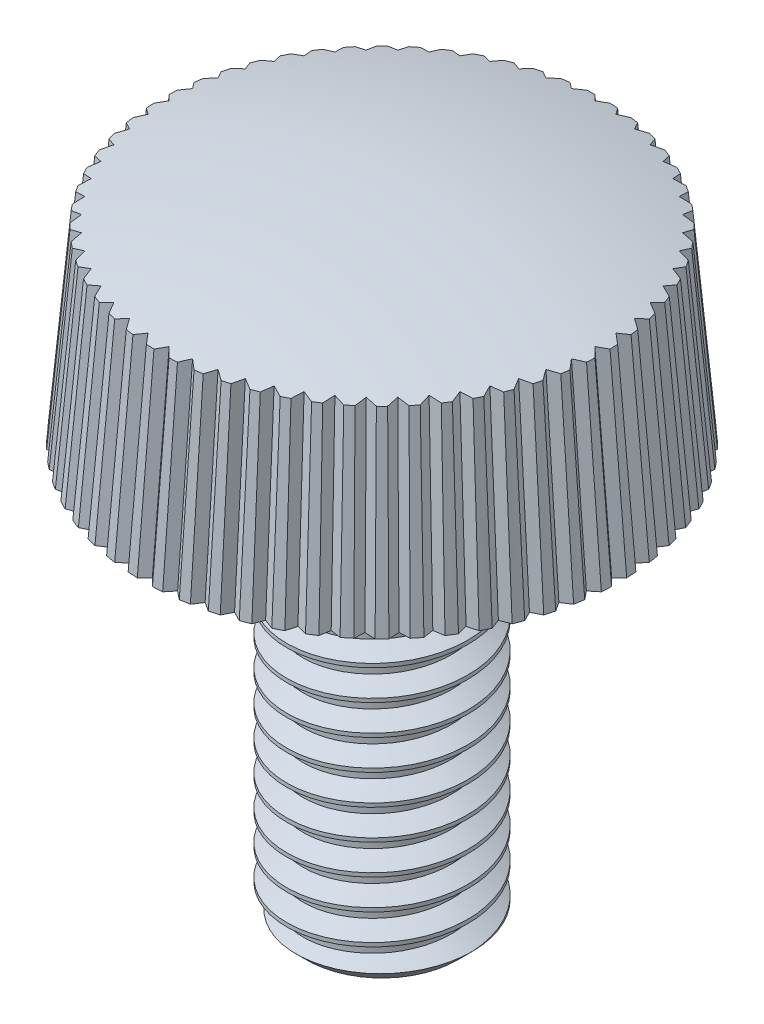
SolidWorks part; units mm, degrees
ref_plane "Front Plane" through (0, 0, 0) normal (0, 0, 1) x (1, 0, 0)
ref_plane "Top Plane" through (0, 0, 0) normal (0, 1, 0) x (1, 0, 0)
ref_plane "Right Plane" through (0, 0, 0) normal (1, 0, 0) x (0, 0, -1)
sketch "Sketch2" plane through (0, 0, 0) normal (0, 0, 1) x (1, 0, 0)
  line L0 (0, 0) -> (0, -2)
  line L1 (0, -2) -> (3.5, -2)
  line L2 (3.5, -2) -> (3.5, -8.78)
  line L3 (3.5, -8.78) -> (5, -8.78)
  line L4 (5, -8.78) -> (5, -7.28)
  line L5 (5, -7.28) -> (7.85, -7.28)
  line L6 (7.85, -7.28) -> (7.3006, -1)
  arc A0 (0, 0) -> (7.3006, -1) centre (0, -27.1492) cw
  dimension "D1" = 3.5
  dimension "D2" = 7.85
  dimension "D3" = 1
  dimension "D4" = 8.78
  dimension "D5" = 1.5
  dimension "D6" = 1.5
  dimension "D7" = 85
  dimension "D8" = 2
revolve "Revolve1" add sketch "Sketch2" angle 360 about L0
sketch "Sketch3" plane through (0, -2, 0) normal (0, -1, 0) x (1, 0, 0)
  circle A0 centre (0, 0) radius 3
  dimension "D1" = 6
extrude "Boss-Extrude1" add sketch "Sketch3" along normal offset from surface (18.78 mm away) 12 up to face at (-5, -8.78, 0) offset beyond the face yes
chamfer "Chamfer1" distance 0.5 angle 45 1 edges at (-3, -20.78, 0)
thread "Thread1" pitch 1 method cut profile "Thread Profile1" start angle 0, offset 1, length 14, pitch 1, diameter 6
ref_plane "Plane1" through (3, -21.28, 0) normal (0, 0, 1) x (1, 0, 0)
sketch "Thread Profile1" plane through (3, -21.28, 0) normal (0, 0, 1) x (1, 0, 0)
  line L0 (0, 0) -> (0, 1) construction
  line L11 (0, 0) -> (0, 0.875)
  line L12 (0, 0.875) -> (-0.5413, 0.5625)
  line L13 (-0.5413, 0.5625) -> (-0.5413, 0.3125)
  line L15 (-0.5413, 0.3125) -> (0, 0)
  line L17 (-0.5413, 0.4375) -> (0, 0.4375) construction
  point P2 (0, 0)
  dimension "Pitch" = 1
  dimension "Profile_Angle" = 60
  dimension "Profile_Land" = 0.25
  dimension "Profile_Height" = 0.5413
ref_plane "Plane2" through (-7.1583, 0.6263, 0) normal (-0.9962, 0.0872, 0) x (0, 0, 1)
sketch "Sketch8" plane through (0, -7.28, 0) normal (0, -1, 0) x (1, 0, 0)
  line L0 (-7.85, 9.8969) -> (-7.85, -9.1444) construction
  circle A0 centre (0, 0) radius 7.85 construction
ref_plane "Plane3" through (-0.6917, -7.9063, 0) normal (0.0872, 0.9962, 0) x (0, 0, -1)
ref_axis "Axis2" through (0, 1.0587, 0) along (0, -1, 0)
sketch "Sketch9" plane through (-0.6917, -7.9063, 0) normal (0.0872, 0.9962, 0) x (0, 0, -1)
  line L0 (0, 13.218) -> (0, -10.7063) construction
  line L1 (0, 6.9356) -> (0.25, 7.1817)
  line L2 (0, 6.9356) -> (-0.25, 7.1817)
  ellipse E0 centre (0, -0.6345) end of major axis (7.85, -0.6345) minor radius 7.8201 construction
  ellipse E1 centre (0, -0.6345) end of major axis (7.85, -0.6345) minor radius 7.8201
  dimension "D1" = 0.25
  dimension "D2" = 0.25
extrude "Cut-Extrude1" cut sketch "Sketch9" along normal up to next contours E1 L0 L1 | L0 E1 L2 region at (-7.7661, -7.2873, -0.0836) region at (-7.7661, -7.2873, 0.0836)
pattern_circular "CirPattern1" count 60 over 360 about axis through (0, 1.0587, 0) along (0, -1, 0) of "Cut-Extrude1"
equation "\"D2@Sketch2\"=15.7/2"
